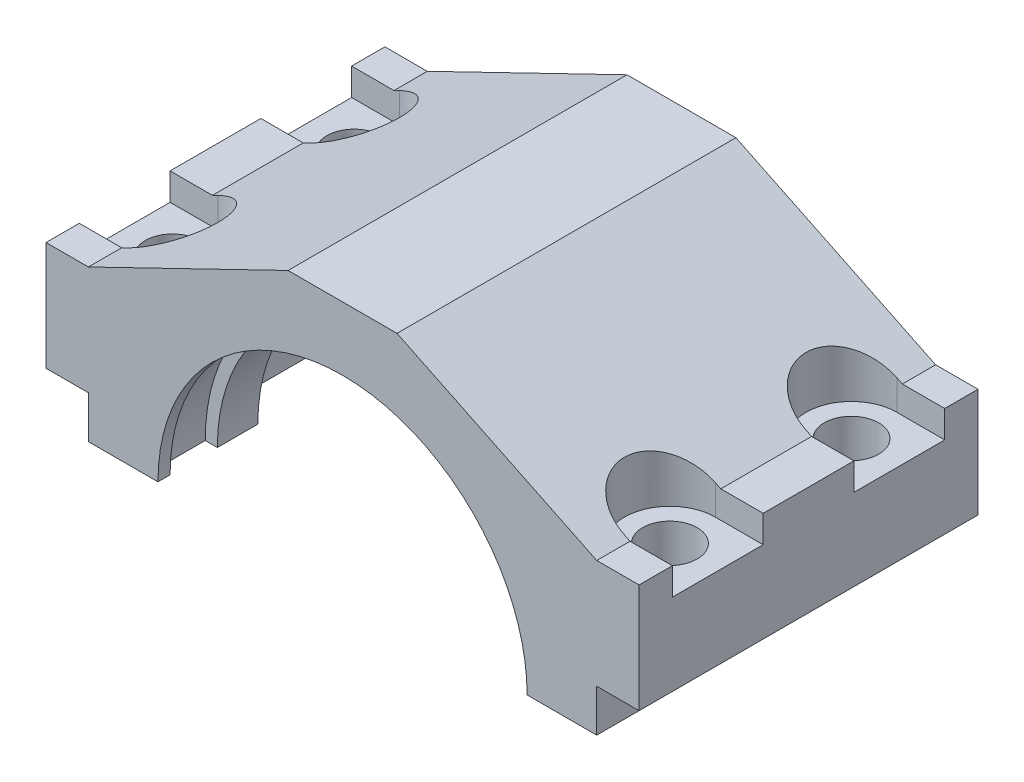
SolidWorks part; units mm, degrees
ref_plane "Front Plane" through (0, 0, 0) normal (0, 0, 1) x (1, 0, 0)
ref_plane "Top Plane" through (0, 0, 0) normal (0, 1, 0) x (1, 0, 0)
ref_plane "Right Plane" through (0, 0, 0) normal (1, 0, 0) x (0, 0, -1)
sketch "Sketch1" plane through (0, 0, 0) normal (0, 0, 1) x (1, 0, 0)
  line L0 (-42, 0) -> (42, 0)
  line L1 (42, 0) -> (42, 7)
  line L2 (42, 7) -> (49, 7)
  line L3 (49, 7) -> (49, 25)
  line L4 (49, 25) -> (42, 25)
  line L5 (42, 25) -> (9, 41)
  line L6 (0, 0) -> (0, 51.1183) construction
  line L7 (-42, 0) -> (-42, 7)
  line L8 (-42, 7) -> (-49, 7)
  line L9 (-49, 7) -> (-49, 25)
  line L10 (-49, 25) -> (-42, 25)
  line L11 (-42, 25) -> (-9, 41)
  line L12 (-9, 41) -> (9, 41)
  point P15 (0, 41)
  dimension "D1" = 42
  dimension "D2" = 7
  dimension "D3" = 7
  dimension "D4" = 18
  dimension "D5" = 7
  dimension "D6" = 18
  dimension "D7" = 41
extrude "Boss-Extrude1" add sketch "Sketch1" against normal mid plane 56
sketch "Sketch2" plane through (0, 0, 28) normal (0, 0, 1) x (1, 0, 0)
  line L0 (-30.5, 0) -> (30.5, 0)
  arc A0 (30.5, 0) -> (-30.5, 0) centre (0, 0) ccw
  dimension "D1" = 61
extrude "Cut-Extrude1" cut sketch "Sketch2" against normal through all
sketch "Sketch3" plane through (0, 0, 0) normal (1, 0, 0) x (0, 0, -1)
  line L0 (28, 30.5) -> (26, 30.5)
  line L1 (28, 25) -> (28, 41) construction
  line L2 (26, 30.5) -> (26, 32.5)
  line L3 (26, 32.5) -> (17, 32.5)
  line L4 (17, 32.5) -> (17, 29.8166)
  line L5 (17, 29.8166) -> (11.5, 29.8166)
  line L6 (11.5, 29.8166) -> (11.5, 36)
  line L7 (11.5, 36) -> (-11.5, 36)
  line L8 (-11.5, 36) -> (-11.5, 29.8166)
  line L9 (-11.5, 29.8166) -> (-18.19, 29.8166)
  line L10 (-18.19, 29.8166) -> (-18.19, 32.5)
  line L11 (-18.19, 32.5) -> (-26, 32.5)
  line L12 (-26, 32.5) -> (-26, 30.5)
  line L13 (-26, 30.5) -> (-28, 30.5)
  line L14 (-28, 25) -> (-28, 41) construction
  line L15 (0, 0) -> (0, 51.3591) construction
  line L16 (28, 0) -> (-28, 0) construction
  line L17 (-28, 30.5) -> (-28, 0)
  line L18 (-28, 0) -> (28, 0)
  line L19 (28, 0) -> (28, 30.5)
  dimension "D1" = 2
  dimension "D2" = 2
  dimension "D3" = 23
  dimension "D4" = 9
  dimension "D5" = 5.5
  dimension "D6" = 7.81
  dimension "D7" = 6.69
  dimension "D8" = 30.5
  dimension "D9" = 32.5
  dimension "D10" = 36
revolve "Cut-Revolve1" cut sketch "Sketch3" angle 360 about L18
sketch "Sketch4" plane through (0, 0, 0) normal (0, 1, 0) x (1, 0, 0)
  line L0 (-56.3495, 0) -> (56.9889, 0) construction
  line L1 (0, 34.2892) -> (0, -39.4047) construction
  line L2 (49, 22.5) -> (41.09, 22.5)
  line L3 (49, 28) -> (49, -28) construction
  line L4 (41.09, 7.5) -> (49, 7.5)
  line L5 (49, 7.5) -> (49, 22.5)
  line L6 (49, -7.5) -> (49, -22.5)
  line L7 (41.09, -7.5) -> (49, -7.5)
  line L8 (49, -22.5) -> (41.09, -22.5)
  line L9 (-49, -22.5) -> (-41.09, -22.5)
  line L10 (-41.09, -7.5) -> (-49, -7.5)
  line L11 (-49, -7.5) -> (-49, -22.5)
  line L12 (-49, 7.5) -> (-49, 22.5)
  line L13 (-41.09, 7.5) -> (-49, 7.5)
  line L14 (-49, 22.5) -> (-41.09, 22.5)
  arc A0 (41.09, 22.5) -> (41.09, 7.5) centre (41.09, 15) ccw
  circle A1 centre (41.09, 15) radius 4.5
  circle A2 centre (41.09, -15) radius 4.5
  arc A3 (41.09, -22.5) -> (41.09, -7.5) centre (41.09, -15) cw
  arc A4 (-41.09, -22.5) -> (-41.09, -7.5) centre (-41.09, -15) ccw
  circle A5 centre (-41.09, -15) radius 4.5
  circle A6 centre (-41.09, 15) radius 4.5
  arc A7 (-41.09, 22.5) -> (-41.09, 7.5) centre (-41.09, 15) cw
  dimension "D2" = 9
  dimension "D3" = 7.5
  dimension "D1" = 7.91
  dimension "D4" = 30
extrude "Cut-Extrude2" cut sketch "Sketch4" against normal blind 4.5 and the other way through all from offset 25 contours L8 A3 L7 L6 | L4 L5 L2 A0 | L9 A4 L10 L11 | A7 L13 L12 L14
extrude "Cut-Extrude3" cut sketch "Sketch4<4>" against normal through all from offset 25 contours A2 | A1 | A5 | A6
sketch "Sketch4<4>" plane through (0, 0, 0) normal (0, 1, 0) x (1, 0, 0) same geometry as "Sketch4"
